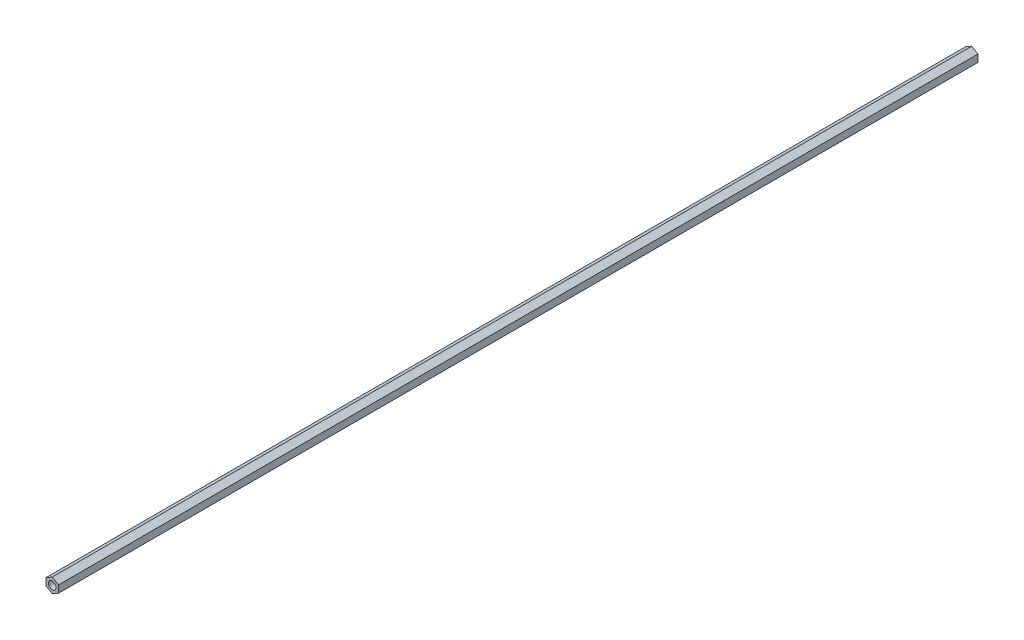
SolidWorks part; units mm, degrees
ref_plane "Front Plane" through (0, 0, 0) normal (0, 0, 1) x (1, 0, 0)
ref_plane "Top Plane" through (0, 0, 0) normal (0, 1, 0) x (1, 0, 0)
ref_plane "Right Plane" through (0, 0, 0) normal (1, 0, 0) x (0, 0, -1)
sketch "Sketch2" plane through (0, 0, 0) normal (0, 0, 1) x (1, 0, 0)
  line L1 (0, 4.7625) -> (-4.1244, 2.3813)
  line L2 (-4.1244, 2.3813) -> (-4.1244, -2.3812)
  line L3 (-4.1244, -2.3812) -> (0, -4.7625)
  line L4 (0, -4.7625) -> (4.1244, -2.3813)
  line L5 (4.1244, -2.3813) -> (4.1244, 2.3813)
  line L6 (4.1244, 2.3813) -> (0, 4.7625)
  circle A0 centre (0, 0) radius 4.1244 construction
  circle A1 centre (0, 0) radius 4.7625 construction
  dimension "D1" = 9.525
extrude "Boss-Extrude1" add sketch "Sketch2" along normal mid plane 604.3625
sketch "Sketch3" plane through (0, 0, 302.1813) normal (0, 0, 1) x (1, 0, 0)
  circle A0 centre (0, 0) radius 2.4892
  dimension "D1" = 4.9784
extrude "Cut-Extrude1" cut sketch "Sketch3" against normal through all
